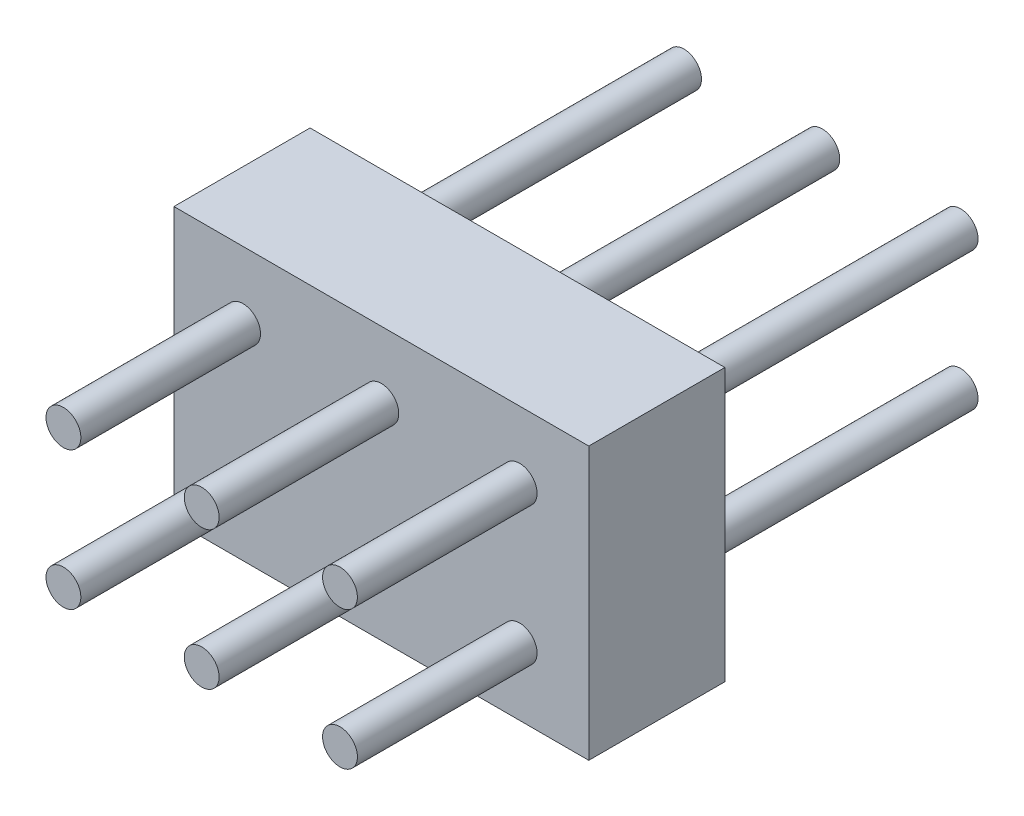
SolidWorks part; units mm, degrees
ref_plane "前视基准面" through (0, 0, 0) normal (0, 0, 1) x (1, 0, 0)
ref_plane "上视基准面" through (0, 0, 0) normal (0, 1, 0) x (1, 0, 0)
ref_plane "右视基准面" through (0, 0, 0) normal (1, 0, 0) x (0, 0, -1)
sketch "Sketch1" plane through (0, 0, 0) normal (0, 0, 1) x (1, 0, 0)
  line L1 (0, 0) -> (7.62, 0)
  line L2 (0, 0) -> (0, 5)
  line L3 (0, 5) -> (7.62, 5)
  line L4 (7.62, 0) -> (7.62, 5)
extrude "Boss-Extrude1" add sketch "Sketch1" along normal blind 2.5
sketch "Sketch2" plane through (0, 0, 2.5) normal (0, 0, 1) x (1, 0, 0)
  line L0 (0, 2.5) -> (8.616, 2.5) construction
  line L1 (0, 5) -> (0, 0) construction
  line L2 (3.81, 5) -> (3.81, -0.5442) construction
  line L4 (7.62, 5) -> (0, 5) construction
  circle A0 centre (1.27, 1.23) radius 0.32
  circle A1 centre (1.27, 3.77) radius 0.32
  circle A2 centre (3.81, 3.77) radius 0.32
  circle A3 centre (3.81, 1.23) radius 0.32
  circle A4 centre (6.35, 3.77) radius 0.32
  circle A5 centre (6.35, 1.23) radius 0.32
  dimension "D1" = 0.64
  dimension "D2" = 1.27
  dimension "D3" = 2.54
  dimension "D4" = 3
extrude "Boss-Extrude2" add sketch "Sketch2" along normal blind 3.3 contours A0 | A3 | A1 | A5 | A4 | A2
extrude "Boss-Extrude3" add sketch "Sketch2<3>" against normal blind 5.6 from surface starting at face at (3.81, 2.5, 0)
sketch "Sketch2<3>" plane through (0, 0, 2.5) normal (0, 0, 1) x (1, 0, 0) same geometry as "Sketch2"
